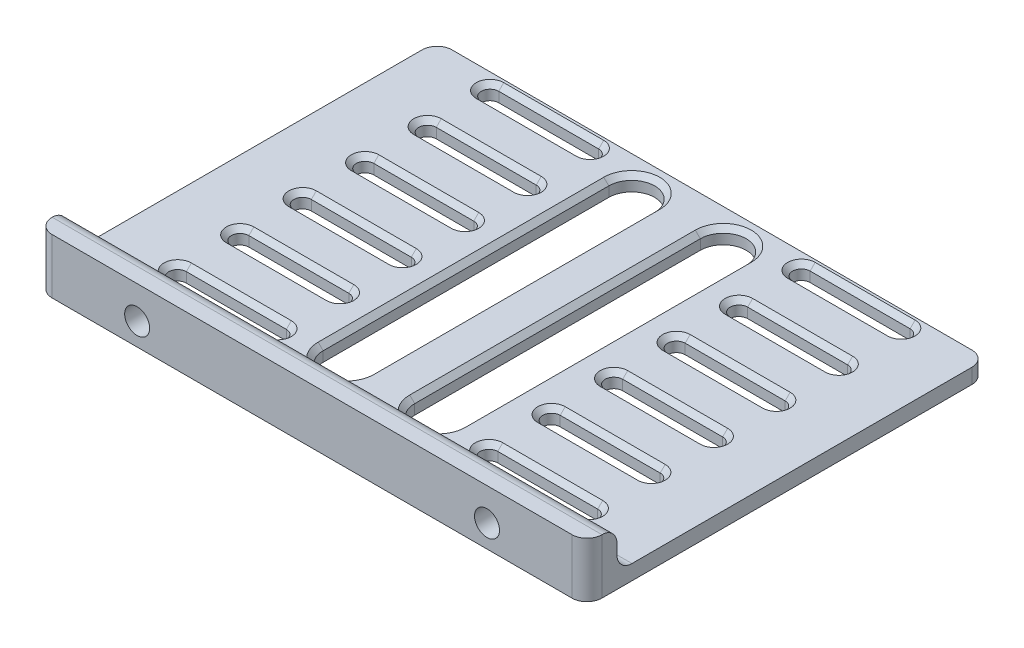
SolidWorks part; units mm, degrees
ref_plane "Front Plane" through (0, 0, 0) normal (0, 0, 1) x (1, 0, 0)
ref_plane "Top Plane" through (0, 0, 0) normal (0, 1, 0) x (1, 0, 0)
ref_plane "Right Plane" through (0, 0, 0) normal (1, 0, 0) x (0, 0, -1)
sketch "Sketch1" plane through (0, 0, 0) normal (0, 1, 0) x (1, 0, 0)
  line L1 (-55, 40) -> (55, 40)
  line L2 (-55, 40) -> (-55, -40)
  line L3 (-55, -40) -> (55, -40)
  line L4 (55, 40) -> (55, -40)
  line L5 (-55, 40) -> (55, -40) construction
  line L6 (-55, -40) -> (55, 40) construction
  point P0 (0, 0)
  dimension "D1" = 110
  dimension "D2" = 80
extrude "Boss-Extrude1" add sketch "Sketch1" along normal blind 3
sketch "Sketch2" plane through (0, 3, 0) normal (0, 1, 0) x (1, 0, 0)
  line L0 (55, -40) -> (55, 40) construction
  line L1 (-55, -40) -> (55, -40)
  line L2 (-55, -40) -> (-55, -34)
  line L3 (-55, -34) -> (55, -34)
  line L4 (55, -40) -> (55, -34)
  dimension "D1" = 6
extrude "Boss-Extrude2" add sketch "Sketch2" along normal blind 8
sketch "Sketch5" plane through (0, 0, 40) normal (0, 0, 1) x (1, 0, 0)
  line L0 (-55, 11) -> (-55, 0) construction
  line L1 (-55, 0) -> (55, 0) construction
  point P0 (-35, 4.5)
  point P2 (35, 4.5)
  dimension "D1" = 20
  dimension "D2" = 70
  dimension "D3" = 4.5
hole_wizard "1/8-27 NPSM Tapped Hole1" positions "Sketch5" profile "Sketch4" tap size "1/8-27 NPSM" standard "ANSI Metric"
cosmetic thread "Hole Thread1" parameters "D1"=20.17, "D2"=10.0838
cosmetic thread "Hole Thread2" parameters "D1"=20.17, "D2"=10.0838
sketch "Sketch4" plane through (-35, 4.5, 40) normal (1, 0, 0) x (0, -1, 0)
  line L0 (0, 0) -> (0, 7.5022)
  line L1 (0, 7.5022) -> (2.5, 6)
  line L2 (2.5, 6) -> (2.5, 0)
  line L5 (2.5, 0) -> (0, 0)
  line L10 (0, 7.5022) -> (-2.5, 6) construction
  line L11 (0, -6.35) -> (0, 107.95) construction
  dimension "Tap Drill Dia." = 5
  dimension "Tap Drill Depth" = 6
  dimension "Drill Angle" = 118
fillet "Fillet1" radius 3 4 edges at (0, 11, 34) (46, 3, 34) (-46, 3, 34) (0, 3, 34)
sketch "Sketch6" plane through (0, 3, 0) normal (0, 1, 0) x (1, 0, 0)
  line L0 (-41.15, -25.75) -> (-21.15, -25.75) construction
  line L1 (-41.15, -24) -> (-21.15, -24)
  line L2 (-41.15, -27.5) -> (-21.15, -27.5)
  line L3 (-55, -40) -> (55, -40) construction
  line L4 (0, -6.05) -> (0, 6.05) construction
  line L5 (41.15, -25.75) -> (21.15, -25.75) construction
  line L6 (41.15, -24) -> (21.15, -24)
  line L7 (41.15, -27.5) -> (21.15, -27.5)
  arc A0 (-41.15, -24) -> (-41.15, -27.5) centre (-41.15, -25.75) ccw
  arc A1 (-21.15, -27.5) -> (-21.15, -24) centre (-21.15, -25.75) ccw
  arc A2 (41.15, -24) -> (41.15, -27.5) centre (41.15, -25.75) cw
  arc A3 (21.15, -27.5) -> (21.15, -24) centre (21.15, -25.75) cw
  point P2 (-31.15, -25.75)
  point P13 (31.15, -25.75)
  dimension "D1" = 20
  dimension "D2" = 3.5
  dimension "D3" = 12.5
extrude "Cut-Extrude1" cut sketch "Sketch6" against normal blind 8
pattern_linear "LPattern1" count 6 spacing 12.5 along (0, 0, -1) of "Cut-Extrude1"
sketch "Sketch7" plane through (0, 3, 0) normal (0, 1, 0) x (1, 0, 0)
  line L0 (-9.1586, -24.0318) -> (-9.1586, 33.1139) construction
  line L1 (-13.7507, -24.0318) -> (-13.7507, 33.1139)
  line L2 (-4.5666, -24.0318) -> (-4.5666, 33.1139)
  line L3 (0, -6.05) -> (0, 6.05) construction
  line L4 (9.1586, -24.0318) -> (9.1586, 33.1139) construction
  line L5 (13.7507, -24.0318) -> (13.7507, 33.1139)
  line L6 (4.5666, -24.0318) -> (4.5666, 33.1139)
  arc A0 (-13.7507, -24.0318) -> (-4.5666, -24.0318) centre (-9.1586, -24.0318) ccw
  arc A1 (-4.5666, 33.1139) -> (-13.7507, 33.1139) centre (-9.1586, 33.1139) ccw
  arc A2 (13.7507, -24.0318) -> (4.5666, -24.0318) centre (9.1586, -24.0318) cw
  arc A3 (4.5666, 33.1139) -> (13.7507, 33.1139) centre (9.1586, 33.1139) cw
  point P2 (-9.1586, 4.541)
  point P11 (9.1586, 4.541)
extrude "Cut-Extrude2" cut sketch "Sketch7" against normal blind 8
fillet "Fillet2" radius 3 4 edges at (-55, 5.5, 40) (55, 5.5, 40) (55, 1.5, -40) (-55, 1.5, -40)
chamfer "Chamfer1" distance 1 angle 45 56 edges at (31.15, 3, 27.5) (42.9, 3, 25.75) (19.4, 3, 25.75) (31.15, 3, 24) (31.15, 3, 15) (42.9, 3, 13.25) (19.4, 3, 13.25) (31.15, 3, 11.5) (31.15, 3, 2.5) (42.9, 3, 0.75) (19.4, 3, 0.75) (31.15, 3, -1) (31.15, 3, -10) (42.9, 3, -11.75) (19.4, 3, -11.75) (31.15, 3, -13.5) (31.15, 3, -22.5) (42.9, 3, -24.25) (19.4, 3, -24.25) (31.15, 3, -26) (31.15, 3, -35) (42.9, 3, -36.75) (19.4, 3, -36.75) (31.15, 3, -38.5) (13.7507, 3, -4.541) (9.1586, 3, -37.706) (9.1586, 3, 28.6239) (4.5666, 3, -4.541) (-4.5666, 3, -4.541) (-9.1586, 3, -37.706) (-9.1586, 3, 28.6239) (-13.7507, 3, -4.541) (-31.15, 3, 27.5) (-19.4, 3, 25.75) (-42.9, 3, 25.75) (-31.15, 3, 24) (-31.15, 3, 15) (-19.4, 3, 13.25) (-42.9, 3, 13.25) (-31.15, 3, 11.5) (-31.15, 3, 2.5) (-19.4, 3, 0.75) (-42.9, 3, 0.75) (-31.15, 3, -1) (-31.15, 3, -10) (-19.4, 3, -11.75) (-42.9, 3, -11.75) (-31.15, 3, -13.5) (-31.15, 3, -22.5) (-19.4, 3, -24.25) (-42.9, 3, -24.25) (-31.15, 3, -26) (-31.15, 3, -35) (-19.4, 3, -36.75) (-42.9, 3, -36.75) (-31.15, 3, -38.5)
